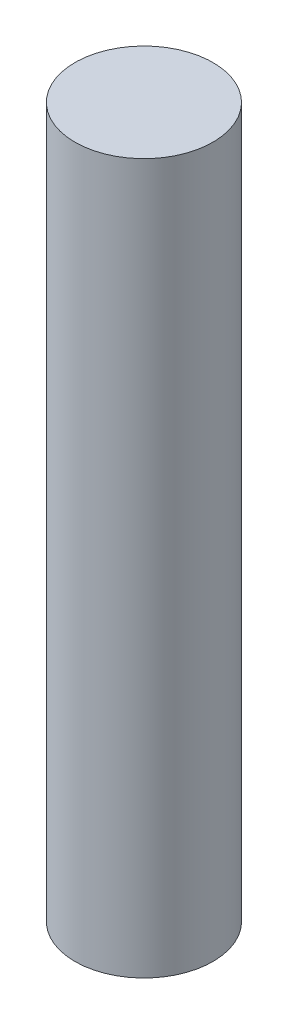
SolidWorks part; units mm, degrees
ref_plane "Front Plane" through (0, 0, 0) normal (0, 0, 1) x (1, 0, 0)
ref_plane "Top Plane" through (0, 0, 0) normal (0, 1, 0) x (1, 0, 0)
ref_plane "Right Plane" through (0, 0, 0) normal (1, 0, 0) x (0, 0, -1)
sketch "Sketch1" plane through (0, 0, 0) normal (0, 1, 0) x (1, 0, 0)
  circle A0 centre (0, 0) radius 12.5
  dimension "D1" = 25
extrude "Boss-Extrude1" add sketch "Sketch1" along normal blind 128.524
